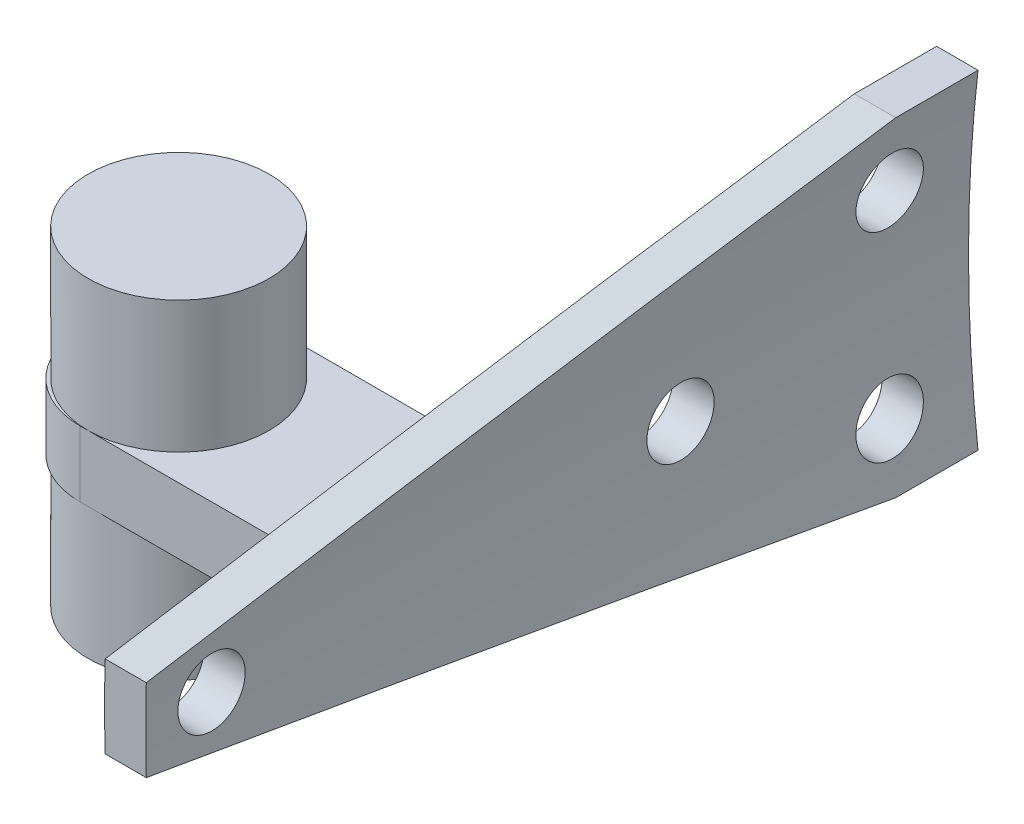
SolidWorks part; units mm, degrees
ref_plane "Front Plane" through (0, 0, 0) normal (0, 0, 1) x (1, 0, 0)
ref_plane "Top Plane" through (0, 0, 0) normal (0, 1, 0) x (1, 0, 0)
ref_plane "Right Plane" through (0, 0, 0) normal (1, 0, 0) x (0, 0, -1)
sketch "Sketch1" plane through (0, 0, 0) normal (0, 0, 1) x (1, 0, 0)
  line L0 (0, 0) -> (-52.4035, 0) construction
  line L1 (-88.9394, 10) -> (-86.4232, 10)
  line L2 (-88.9394, -10) -> (-86.4232, -10)
  arc A0 (-86.4232, 10) -> (-86.4232, -10) centre (0, 0) ccw
  arc A1 (-88.9394, 10) -> (-88.9394, -10) centre (0, 0) ccw
  dimension "D1" = 2.5
  dimension "D2" = 86.9998
  dimension "D3" = 20
extrude "Boss-Extrude1" add sketch "Sketch1" along normal blind 50
sketch "Sketch2" plane through (0, 0, 0) normal (1, 0, 0) x (0, 0, -1)
  line L0 (0, 10) -> (0, -10)
  line L1 (0, 10) -> (-50, 10) construction
  line L2 (0, 10) -> (0, -10) construction
  line L3 (0, -10) -> (-50, -10) construction
  line L4 (-50, 10) -> (-50, -10) construction
  line L5 (0, -10) -> (-5, -10)
  line L6 (-5, -10) -> (-50, -2.5)
  line L7 (-50, -2.5) -> (-50, 2.5)
  line L8 (-50, 2.5) -> (-5, 10)
  line L9 (-5, 10) -> (0, 10)
  line L10 (0, 0) -> (-50.031, 0) construction
  line L12 (-88.7937, 27.6855) -> (20.3533, 27.6855)
  line L13 (-88.7937, 27.6855) -> (-88.7937, -33.0502)
  line L14 (-88.7937, -33.0502) -> (20.3533, -33.0502)
  line L15 (20.3533, 27.6855) -> (20.3533, -33.0502)
  dimension "D1" = 5
extrude "Cut-Extrude1" cut sketch "Sketch2" against normal through all
hole_wizard "#20 (0.161) Diameter Hole1" positions "Sketch5" profile "Sketch4" hole size "#20" standard "ANSI Inch" end condition through all
sketch "Sketch5" plane through (0, 0, 0) normal (1, 0, 0) x (0, 0, -1)
  line L1 (0, -10) -> (-42.3856, -10)
  line L2 (0, -10) -> (0, 10)
  line L3 (0, 10) -> (-42.3856, 10)
  line L4 (-42.3856, -10) -> (-42.3856, 10)
  line L7 (-5, 10) -> (0, 10) construction
  line L8 (0, 0) -> (-42.3856, 0)
  line L10 (-5, 6) -> (-5, -6)
  line L11 (-50, 2.5) -> (-50, -2.5) construction
  point P0 (-46, 0)
  point P164 (-5, 6)
  point P165 (-5, -6)
  point P172 (-5, 0)
  point P177 (-17.5, 0)
  dimension "D1" = 5
  dimension "D2" = 4
  dimension "D3" = 4
  dimension "D4" = 12.5
sketch "Sketch4" plane through (0, 0, 46) normal (0, 1, 0) x (0, 0, -1)
  line L0 (0, 0) -> (0, 89.4998)
  line L1 (0, 89.4998) -> (2.0447, 89.4998)
  line L2 (2.0447, 89.4998) -> (2.0447, 0)
  line L5 (2.0447, 0) -> (0, 0)
  line L11 (0, -6.35) -> (0, 107.95) construction
  dimension "Thru Hole Dia." = 4.0894
  dimension "Thru Hole Depth" = 89.4998
ref_plane "Plane1" through (-87.9998, 0, 0) normal (1, 0, 0) x (0, 0, -1)
sketch "Sketch7" plane through (-87.9998, 0, -87.9998) normal (1, 0, 0) x (0, 0, -1)
  line L0 (-87.9998, 0) -> (-80.3469, 0) construction
  line L1 (-125.9998, 2) -> (-114.9998, 2)
  line L2 (-125.9998, 2) -> (-125.9998, -2)
  line L3 (-125.9998, -2) -> (-114.9998, -2)
  line L4 (-114.9998, 2) -> (-114.9998, -2)
  line L5 (-87.9998, 10) -> (-87.9998, -10) construction
  line L6 (-87.9998, -10) -> (-87.9998, 10) construction
  circle A2 centre (-133.9998, 0) radius 2.0447 construction
  point P7 (0, 0)
  point P8 (-125.9998, 0)
  point P17 (0, 0)
  dimension "D2" = 11
  dimension "D1" = 4
  dimension "D3" = 8
extrude "Boss-Extrude2" add sketch "Sketch7" against normal blind 20
fillet "Fillet1" radius 2 4 edges at (-89.4775, 2, 32.5) (-89.4998, 0, 38) (-89.4998, 0, 27) (-89.4775, -2, 32.5)
sketch "Sketch8" plane through (0, -2, 0) normal (0, -1, 0) x (1, 0, 0)
  line L1 (-96.9998, 27) -> (-107.9998, 27) construction
  line L2 (-96.9998, 27) -> (-96.9998, 38) construction
  line L3 (-96.9998, 38) -> (-107.9998, 38) construction
  line L4 (-107.9998, 27) -> (-107.9998, 38) construction
  line L5 (-96.9998, 27) -> (-107.9998, 38) construction
  line L6 (-96.9998, 38) -> (-107.9998, 27) construction
  circle A0 centre (-102.4998, 32.5) radius 5.5
  point P0 (-102.4998, 32.5)
extrude "Boss-Extrude3" add sketch "Sketch8" along normal blind 8 and the other way blind 12
fillet "Fillet2" radius 5 2 edges at (-107.9998, 0, 38) (-107.9998, 0, 27)
